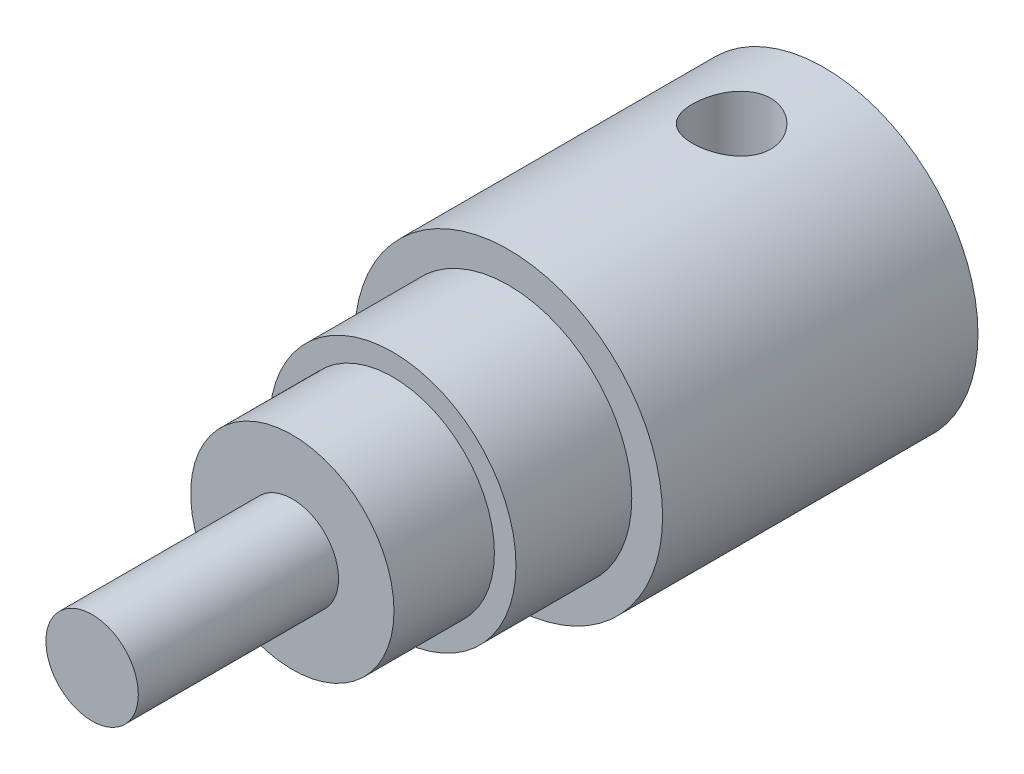
SolidWorks part; units mm, degrees
ref_plane "Plan de face" through (0, 0, 0) normal (0, 0, 1) x (1, 0, 0)
ref_plane "Plan de dessus" through (0, 0, 0) normal (0, 1, 0) x (1, 0, 0)
ref_plane "Plan de droite" through (0, 0, 0) normal (1, 0, 0) x (0, 0, -1)
sketch "Esquisse1" plane through (0, 0, 0) normal (0, 0, 1) x (1, 0, 0)
  circle A0 centre (0, 0) radius 25
extrude "Boss.-Extru.1" add sketch "Esquisse1" along normal blind 51.2
sketch "Esquisse2" plane through (0, 0, 51.2) normal (0, 0, 1) x (1, 0, 0)
  circle A0 centre (0, 0) radius 20
extrude "Boss.-Extru.2" add sketch "Esquisse2" along normal blind 18.8
sketch "Esquisse3" plane through (0, 0, 70) normal (0, 0, 1) x (1, 0, 0)
  circle A0 centre (0, 0) radius 16.5
extrude "Boss.-Extru.3" add sketch "Esquisse3" along normal blind 16.7
sketch "Esquisse4" plane through (0, 0, 86.7) normal (0, 0, 1) x (1, 0, 0)
  circle A0 centre (0, 0) radius 27.5
extrude "Boss.-Extru.4" add sketch "Esquisse4" along normal blind 47.1
chamfer "Chanfrein1" distance 10 angle 60 1 edges at (27.5, 0, 86.7) first distance on face at (16.5, 0, 86.7)
sketch "Esquisse12" plane through (0, 0, 0) normal (0, 1, 0) x (1, 0, 0)
  line L0 (0, -30.25) -> (0, 30.25) construction
  line L1 (-30.25, 0) -> (30.25, 0) construction
  circle A0 centre (0, -15) radius 6.35
  point P0 (0, -15)
  dimension "D1" = 15
extrude "Enlèv. mat.-Extru.1" cut sketch "Esquisse12" against normal through all both and the other way through all
sketch "Esquisse13" plane through (0, 0, 133.8) normal (0, 0, 1) x (1, 0, 0)
  line L0 (30.25, 0) -> (-30.25, 0) construction
  circle A0 centre (0.544, 0) radius 47.2584
extrude "Enlèv. mat.-Extru.2" cut sketch "Esquisse13" against normal blind 15 contours A0
sketch "Esquisse14" plane through (0, 0, 118.8) normal (0, 0, 1) x (1, 0, 0)
  circle A0 centre (0, 0) radius 7.5
  circle A1 centre (0, 0) radius 39.9347
  dimension "15" = 15
extrude "Enlèv. mat.-Extru.4" cut sketch "Esquisse14" against normal blind 32.5 contours A0 | A1
